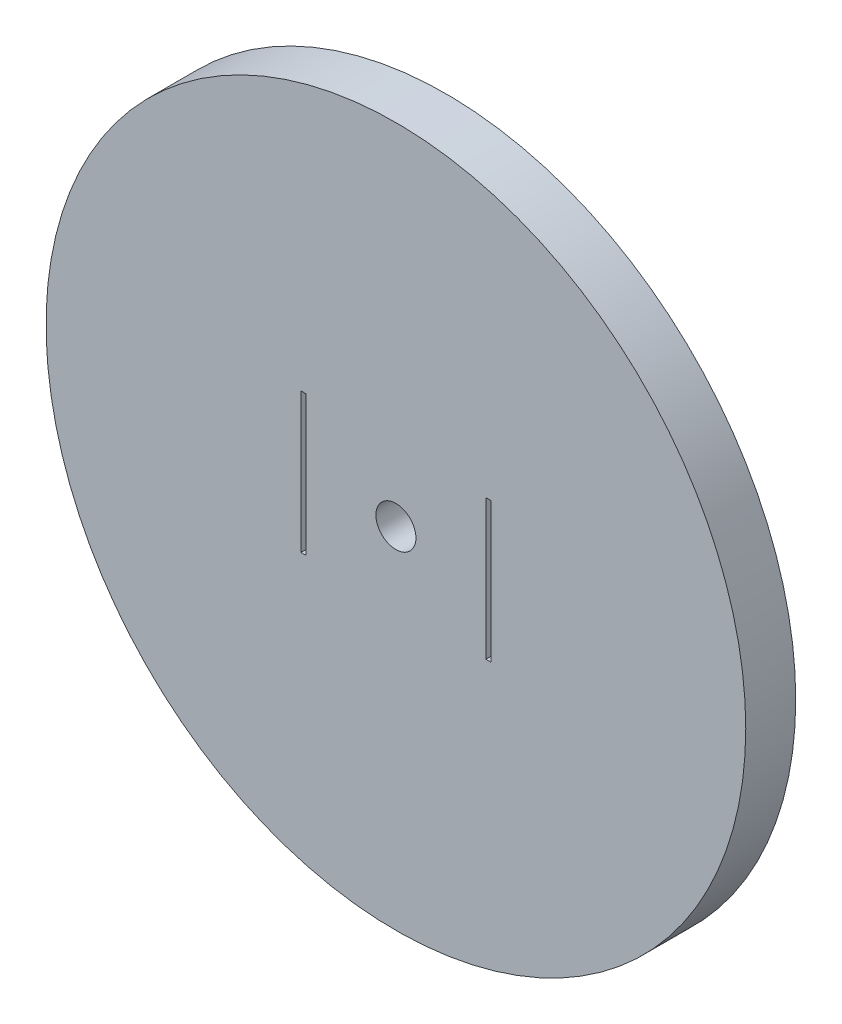
SolidWorks part; units mm, degrees
ref_plane "Front Plane" through (0, 0, 0) normal (0, 0, 1) x (1, 0, 0)
ref_plane "Top Plane" through (0, 0, 0) normal (0, 1, 0) x (1, 0, 0)
ref_plane "Right Plane" through (0, 0, 0) normal (1, 0, 0) x (0, 0, -1)
sketch "Sketch1" plane through (0, 0, 0) normal (0, 0, 1) x (1, 0, 0)
  line L0 (0, 10.3237) -> (0, -11.9962) construction
  line L1 (-9.5, 7) -> (-9, 7)
  line L2 (-9.5, 7) -> (-9.5, -7)
  line L3 (-9.5, -7) -> (-9, -7)
  line L4 (-9, 7) -> (-9, -7)
  line L5 (9, 7) -> (9, -7)
  line L6 (9.5, -7) -> (9, -7)
  line L7 (9.5, 7) -> (9.5, -7)
  line L8 (9.5, 7) -> (9, 7)
  circle A0 centre (0, 0) radius 35
  circle A1 centre (0, 0) radius 2
  dimension "D1" = 4
  dimension "D2" = 70
  dimension "D3" = 0.5
  dimension "D4" = 9
  dimension "D5" = 7
  dimension "D6" = 7
extrude "Boss-Extrude1" add sketch "Sketch1" along normal blind 5
sketch "Sketch3" plane through (0, 0, 0) normal (0, 1, 0) x (1, 0, 0)
  line L0 (-20, 14.6321) -> (-20, 0) construction
  line L1 (35, 0) -> (-35, 0) construction
  line L2 (-24.35, 14.6321) -> (-24.35, 0)
  line L3 (-24.35, 0) -> (-20, 0)
  line L4 (-20, 0) -> (-20, 18.9821)
  circle A0 centre (-20, 14.6321) radius 4.35 construction
  arc A1 (-24.35, 14.6321) -> (-20, 18.9821) centre (-20, 14.6321) cw
  dimension "D1" = 8.7
revolve "Revolve1" add sketch "Sketch3" angle 360 about L0
